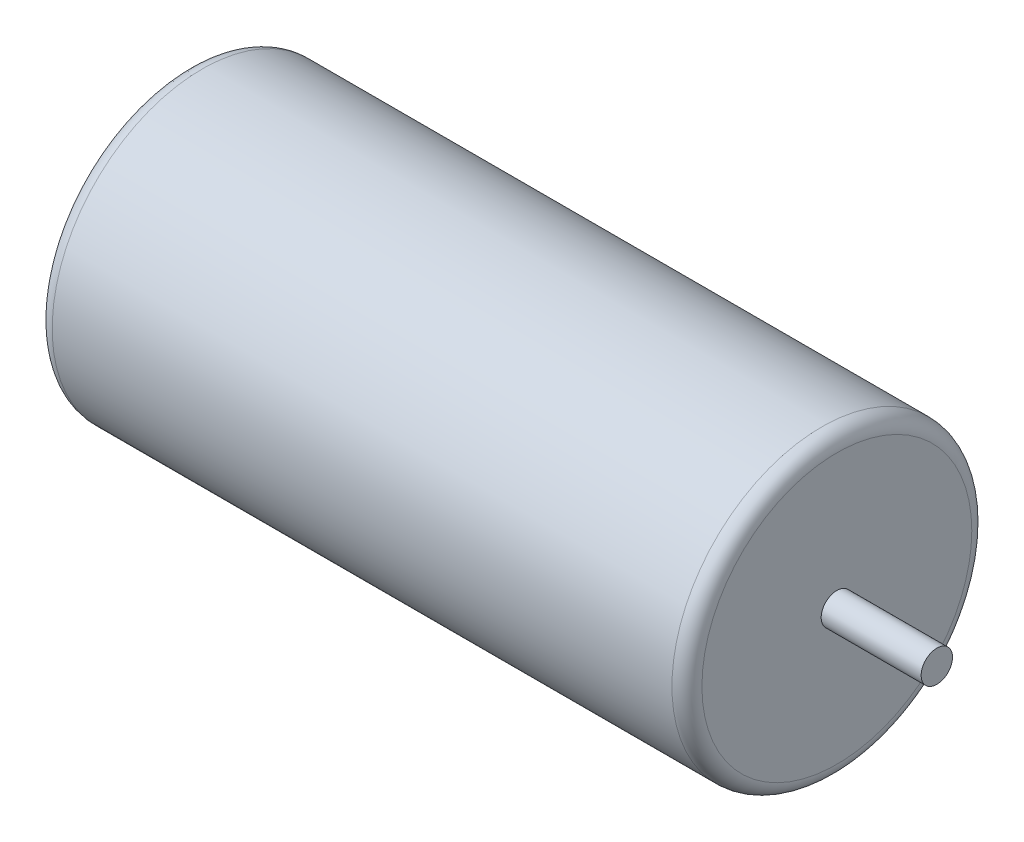
SolidWorks part; units mm, degrees
material "6061-T6 (SS)"
ref_plane "Front Plane" through (0, 0, 0) normal (0, 0, 1) x (1, 0, 0)
ref_plane "Top Plane" through (0, 0, 0) normal (0, 1, 0) x (1, 0, 0)
ref_plane "Right Plane" through (0, 0, 0) normal (1, 0, 0) x (0, 0, -1)
sketch "Sketch1" plane through (0, 0, 0) normal (1, 0, 0) x (0, 0, -1)
  circle A0 centre (0, 0) radius 38.1
  dimension "D1" = 76.2
extrude "Boss-Extrude1" add sketch "Sketch1" along normal blind 165.1
sketch "Sketch2" plane through (165.1, 0, 0) normal (1, 0, 0) x (0, 0, -1)
  circle A0 centre (0, 0) radius 3.9878
  dimension "D1" = 7.9756
extrude "Boss-Extrude2" add sketch "Sketch2" along normal blind 25.4
fillet "Fillet1" radius 3.81 2 edges at (165.1, 0, -38.1) (0, 0, -38.1)
sketch "Sketch4" plane through (0, 0, 0) normal (0, 0, 1) x (1, 0, 0)
  line L0 (-73.9192, 0) -> (225.5705, 0) construction
sketch "Sketch5" plane through (190.5, 0, 0) normal (1, 0, 0) x (0, 0, -1)
  line L0 (0, -53.4374) -> (0, 75.7686) construction
shell "Shell2" thickness 5.08 removed face at (0, 0, -34.29)
